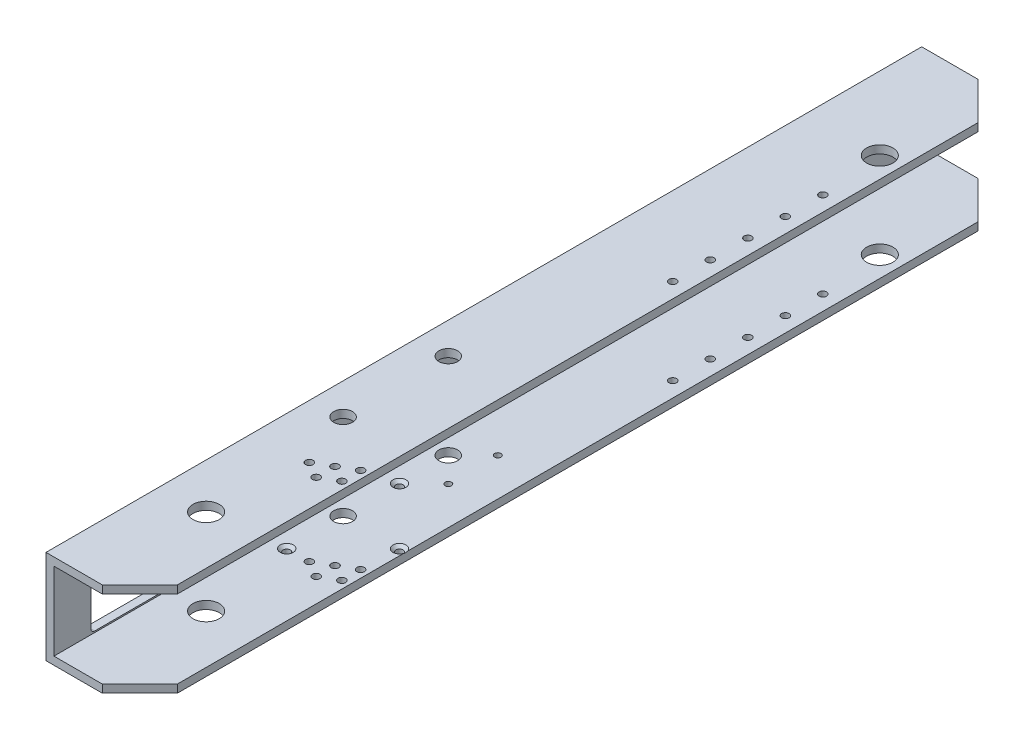
SolidWorks part; units mm, degrees
ref_plane "Front Plane" through (0, 0, 0) normal (0, 0, 1) x (1, 0, 0)
ref_plane "Top Plane" through (0, 0, 0) normal (0, 1, 0) x (1, 0, 0)
ref_plane "Right Plane" through (0, 0, 0) normal (1, 0, 0) x (0, 0, -1)
sketch "Sketch1" plane through (0, 0, 0) normal (0, 0, 1) x (1, 0, 0)
  line L0 (0, -37.5) -> (0, 37.5)
  line L1 (0, 37.5) -> (75, 37.5)
  line L2 (75, 37.5) -> (75, 31.15)
  line L3 (75, 31.15) -> (6.35, 31.15)
  line L4 (6.35, 31.15) -> (6.35, -31.15)
  line L5 (6.35, -31.15) -> (75, -31.15)
  line L6 (75, -31.15) -> (75, -37.5)
  line L7 (75, -37.5) -> (0, -37.5)
  line L8 (0, 0) -> (6.35, 0) construction
  dimension "D1" = 75
  dimension "D2" = 75
  dimension "D3" = 6.35
extrude "Boss-Extrude1" add sketch "Sketch1" along normal blind 700
sketch "Sketch3" plane through (0, 0, 0) normal (-1, 0, 0) x (0, 0, 1)
  line L0 (29.5, -30) -> (154.5, -30) construction
  line L1 (29.5, -30) -> (29.5, 30) construction
  line L2 (154.5, -30) -> (154.5, 30) construction
  line L3 (29.5, 30) -> (154.5, 30) construction
  line L4 (29.5, -30) -> (154.5, 30) construction
  line L5 (154.5, -30) -> (29.5, 30) construction
  line L6 (350, -37.5) -> (350, 96.3047) construction
  line L7 (700, -37.5) -> (0, -37.5) construction
  line L8 (0, 0) -> (92, 0) construction
  line L9 (670.5, -30) -> (545.5, -30)
  line L10 (545.5, 4.15) -> (545.5, 30)
  line L11 (670.5, 30) -> (545.5, 30)
  line L12 (670.5, -30) -> (670.5, 30)
  line L14 (460, 4.15) -> (355, 4.15)
  line L15 (460, 4.15) -> (460, -16.85) construction
  line L16 (355, 4.15) -> (355, -16.85)
  line L17 (395.5, -30) -> (395.5, -16.85)
  line L18 (460, 4.15) -> (355, -16.85) construction
  line L19 (355, 4.15) -> (460, -16.85) construction
  line L31 (395.5, -16.85) -> (355, -16.85)
  line L32 (460, 4.15) -> (545.5, 4.15)
  line L39 (545.5, -30) -> (395.5, -30)
  line L42 (407.5, -6.35) -> (407.5, 17.65) construction
  line L43 (608, 30) -> (608, -6.35) construction
  point P1 (92, 0)
  point P19 (407.5, -6.35)
  point P28 (407.5, 17.65)
  dimension "D1" = 60
  dimension "D2" = 258
  dimension "D3" = 125
  dimension "D4" = 20.65
  dimension "D5" = 105
  dimension "D7" = 21
  dimension "D10" = 150
  dimension "D11" = 200.5
extrude "Cut-Extrude1" cut sketch "Sketch3" against normal through all
chamfer "Chamfer1" distance 30 angle 45 4 edges at (75, 34.325, 700) (75, -34.325, 700) (75, -34.325, 0) (75, 34.325, 0)
sketch "Sketch4" plane through (0, 37.5, 0) normal (0, 1, 0) x (1, 0, 0)
  line L0 (75, -608) -> (36, -608) construction
  line L1 (75, -670) -> (75, -30) construction
  line L2 (0, -670.5) -> (0, -545.5) construction
  line L3 (58.5, -92) -> (58.5, -350) construction
  line L4 (0, -545.0695) -> (0, -670.9305) construction
  line L5 (0, -700) -> (0, 0) construction
  line L6 (0, -608) -> (36, -608) construction
  line L7 (0, -350) -> (49.4239, -350) construction
  line L8 (36, -608) -> (36, -350) construction
  line L9 (98.5, -92) -> (98.5, -608) construction
  line L10 (69, -92) -> (75, -92) construction
  line L11 (75, -670) -> (75, -30) construction
  circle A0 centre (36, -608) radius 10.5
  circle A1 centre (36, -608) radius 62.5 construction
  circle A2 centre (36, -608) radius 72.5 construction
  circle A3 centre (58.5, -92) radius 10.5
  circle A4 centre (58.5, -92) radius 40 construction
  dimension "D1" = 21
  dimension "D2" = 125
  dimension "D3" = 145
  dimension "D6" = 80
  dimension "D4" = 125.861
  dimension "D5" = 39
  dimension "D7" = 6
extrude "Cut-Extrude2" cut sketch "Sketch4" against normal through all
sketch "Sketch5" plane through (0, -37.5, 0) normal (0, -1, 0) x (1, 0, 0)
  line L0 (0, 700) -> (0, 0) construction
  line L1 (0, 403.3981) -> (24.9518, 403.3981) construction
  line L6 (75, 670) -> (75, 30) construction
  line L7 (36, 608) -> (24.9518, 403.3981) construction
  line L8 (24.9518, 403.3981) -> (58.5, 92) construction
  circle A0 centre (25, 487.4981) radius 7.5
  circle A2 centre (24.9518, 403.3981) radius 7.5
  point P10 (58.5, 92)
  point P11 (36, 608)
  dimension "D1" = 15
  dimension "D2" = 50
  dimension "D3" = 84.1
  dimension "D4" = 24.9518
  dimension "D5" = 204.9
  dimension "D6" = 313.2
extrude "Cut-Extrude3" cut sketch "Sketch5" against normal through all
chamfer "Chamfer2" distance 3 angle 45 3 edges at (6.35, 17.075, 545.5) (6.35, -23.425, 395.5) (6.35, -6.35, 355)
fillet "Fillet1" radius 3 6 edges at (1.675, -16.85, 355) (1.675, 4.15, 355) (3.175, 30, 670.5) (3.175, -30, 670.5) (1.675, 30, 545.5) (1.675, -30, 395.5)
sketch "Sketch6" plane through (0, 37.5, 0) normal (0, 1, 0) x (1, 0, 0)
  line L0 (75, -670) -> (75, -30) construction
  line L1 (69, -517.4981) -> (69, -532.4981) construction
  line L2 (69, -532.4981) -> (56.0096, -524.9981) construction
  line L3 (56.0096, -524.9981) -> (56.0096, -539.9981) construction
  line L4 (56.0096, -539.9981) -> (69, -532.4981) construction
  line L5 (63, -262) -> (63, -232) construction
  line L6 (63, -232) -> (63, -202) construction
  line L7 (63, -202) -> (63, -172) construction
  line L8 (63, -172) -> (63, -142) construction
  line L10 (56.0096, -539.9981) -> (43.0192, -532.4981) construction
  line L11 (43.0192, -532.4981) -> (56.0096, -524.9981) construction
  circle A0 centre (69, -517.4981) radius 3
  circle A1 centre (25, -487.4981) radius 7.5 construction
  circle A2 centre (69, -532.4981) radius 3
  circle A3 centre (56.0096, -524.9981) radius 3
  circle A4 centre (56.0096, -539.9981) radius 3
  circle A5 centre (63, -262) radius 3
  circle A6 centre (63, -232) radius 3
  circle A7 centre (63, -202) radius 3
  circle A8 centre (63, -172) radius 3
  circle A9 centre (63, -142) radius 3
  circle A10 centre (58.5, -92) radius 10.5 construction
  circle A12 centre (43.0192, -532.4981) radius 3
  dimension "D1" = 6
  dimension "D6" = 50
  dimension "D2" = 6
  dimension "D3" = 30
  dimension "D4" = 15
  dimension "D5" = 30
  dimension "D8" = 12
extrude "tensioner holes" cut sketch "Sketch6" against normal through all
hole_wizard "CSK for M5 Countersunk Flat Head Screw1" positions "Sketch9" profile "Sketch10" countersink size "M5" standard "ISO"
sketch "Sketch9" plane through (0, -31.15, 0) normal (0, -1, 0) x (-1, 0, 0)
  line L0 (-25, -532.5731) -> (-25, -487.4981) construction
  line L1 (-25, -487.4981) -> (-70.075, -487.4981) construction
  line L2 (-70.075, -487.4981) -> (-25, -442.4231) construction
  line L3 (-25, -442.4231) -> (-25, -487.4981) construction
  point P0 (-25, -532.5731)
  point P2 (-25, -442.4231)
  point P4 (-70.075, -487.4981)
  dimension "D1" = 90.15
sketch "Sketch10" plane through (25, -31.15, 532.5731) normal (1, 0, 0) x (0, 0, 1)
  line L0 (0, 0) -> (0, 13.7425)
  line L1 (0, 13.7425) -> (2.9, 12)
  line L2 (2.9, 12) -> (2.9, 2.3)
  line L3 (2.9, 2.3) -> (5.2, 0)
  line L5 (5.2, 0) -> (0, 0)
  line L6 (-2.9, 2.3) -> (-5.2, 0) construction
  line L10 (0, 13.7425) -> (-2.9, 12) construction
  line L11 (0, -6.35) -> (0, 107.95) construction
  dimension "Hole Dia." = 5.8
  dimension "Hole Depth" = 12
  dimension "Near C'Sink Dia." = 10.4
  dimension "Near C'Sink Angle" = 90
  dimension "Drill Angle" = 118
sketch "Sketch11" plane through (0, 0, 0) normal (-1, 0, 0) x (0, 0, 1)
  line L0 (700, -24) -> (0, -24) construction
  line L3 (0, 37.5) -> (0, -37.5) construction
  line L6 (700, 37.5) -> (700, -37.5) construction
  line L7 (350, -16.85) -> (350, -31.15) construction
  line L8 (358, -16.85) -> (395.5, -16.85) construction
  line L9 (700, -31.15) -> (0, -31.15) construction
  line L10 (700, -37.5) -> (0, -37.5) construction
  line L11 (13.5, -37.5) -> (350, -37.5) construction
  line L13 (181.75, -24) -> (181.75, -37.5) construction
  circle A0 centre (350, -24) radius 3
  circle A1 centre (13.5, -24) radius 3
  circle A2 centre (13.5, -24) radius 13.5 construction
  circle A3 centre (181.75, -24) radius 3
  dimension "D1" = 6
extrude "Cut-Extrude4" cut sketch "Sketch11" against normal blind 10
sketch "Sketch12" plane through (0, 0, 0) normal (-1, 0, 0) x (0, 0, 1)
  line L0 (674.511, -31.0618) -> (354.1412, -31.0618)
  line L1 (674.511, -31.0618) -> (674.511, 32.1701)
  line L2 (354.1412, -31.0618) -> (354.1412, 32.1701)
  line L3 (674.511, 32.1701) -> (354.1412, 32.1701)
  line L4 (674.511, -31.0618) -> (354.1412, 32.1701) construction
  line L5 (354.1412, -31.0618) -> (674.511, 32.1701) construction
  circle A0 centre (667.5, -27) radius 2.995
  circle A1 centre (667.5, 27) radius 2.995
  circle A2 centre (548.5, 27) radius 2.995
  circle A3 centre (358, 1.15) radius 2.995
  circle A4 centre (358, -13.85) radius 2.995
  circle A5 centre (398.5, -27) radius 2.995
  point P19 (514.3261, 0.5542)
  dimension "D1" = 5.99
extrude "Boss-Extrude2" [suppressed] add sketch "Sketch12" against normal blind 1 from offset 1 offset against normal yes
sketch "Sketch13" plane through (0, -37.5, 0) normal (0, -1, 0) x (1, 0, 0)
  line L0 (44.7508, 423.1971) -> (5.1528, 423.1971) construction
  line L1 (44.7508, 423.1971) -> (44.7508, 383.5991) construction
  line L2 (5.1528, 423.1971) -> (5.1528, 383.5991) construction
  line L3 (44.7508, 383.5991) -> (5.1528, 383.5991) construction
  line L4 (44.7508, 423.1971) -> (5.1528, 383.5991) construction
  line L5 (5.1528, 423.1971) -> (44.7508, 383.5991) construction
  circle A0 centre (5.1528, 423.1971) radius 2.55
  circle A1 centre (5.1528, 383.5991) radius 2.55
  circle A2 centre (44.7508, 383.5991) radius 2.55
  circle A3 centre (44.7508, 423.1971) radius 2.55
  circle A4 centre (24.9518, 403.3981) radius 7.5 construction
  point P9 (24.9518, 403.3981)
  dimension "D2" = 5.1
  dimension "D1" = 56
extrude "Cut-Extrude5" cut sketch "Sketch13" against normal blind 10
move or copy body "Body-Move/Copy1" [suppressed] bodies to move or copy 113
